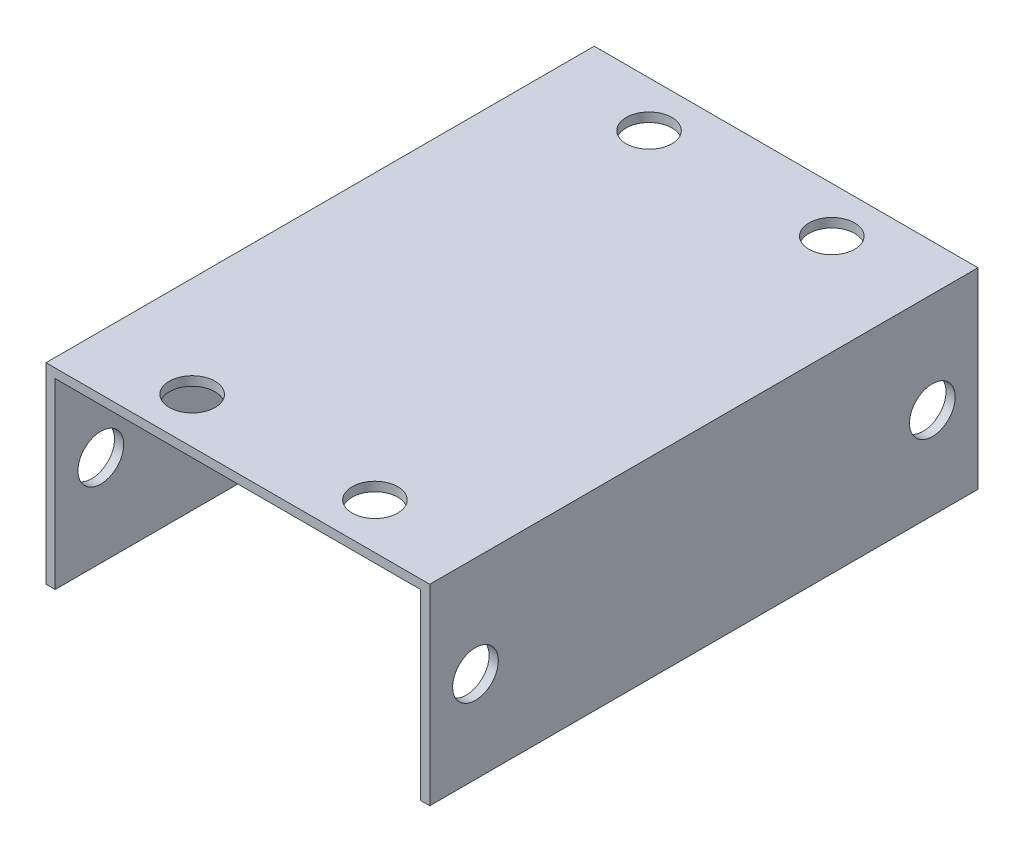
SolidWorks part; units mm, degrees
ref_plane "Front Plane" through (0, 0, 0) normal (0, 0, 1) x (1, 0, 0)
ref_plane "Top Plane" through (0, 0, 0) normal (0, 1, 0) x (1, 0, 0)
ref_plane "Right Plane" through (0, 0, 0) normal (1, 0, 0) x (0, 0, -1)
sketch "Sketch1" plane through (0, 0, 0) normal (0, 0, 1) x (1, 0, 0)
  line L0 (-20, -10) -> (20, -10) construction
  line L1 (-20, -10) -> (20, -10) construction
  line L2 (-20, -10) -> (-20, 10)
  line L3 (-20, 10) -> (20, 10)
  line L4 (20, -10) -> (20, 10)
  line L5 (-20, -10) -> (20, 10) construction
  line L6 (-20, 10) -> (20, -10) construction
  line L7 (-21, -10) -> (-20, -10)
  line L8 (-21, -10) -> (-21, 11)
  line L9 (-21, 11) -> (21, 11)
  line L10 (21, -10) -> (21, 11)
  line L11 (-21, -10) -> (21, 11) construction
  line L12 (-21, 11) -> (21, -10) construction
  line L13 (20, -10) -> (21, -10)
  point P0 (0, 0)
  point P6 (0, 0.5)
  point P11 (-3.491, 1.1742)
  point P12 (0, 0)
  point P13 (0, 0)
  point P14 (0, 0)
  dimension "D1" = 1
  dimension "D2" = 1
  dimension "D3" = 40
  dimension "D4" = 20
extrude "Boss-Extrude1" add sketch "Sketch1" along normal blind 60
sketch "Sketch2" plane through (0, 10, 0) normal (0, -1, 0) x (1, 0, 0)
  line L1 (-20, 60) -> (-20, 0) construction
  line L3 (-20, 0) -> (20, 0) construction
  line L4 (0, 30) -> (0, 0) construction
  line L5 (20, 60) -> (20, 0) construction
  line L6 (-20, 30) -> (20, 30) construction
  line L7 (-20, 5) -> (0, 5) construction
  circle A3 centre (-10, 5) radius 2.5
  circle A4 centre (10, 5) radius 2.5
  circle A5 centre (10, 55) radius 2.5
  circle A6 centre (-10, 55) radius 2.5
  point P20 (-11.2884, 5)
  dimension "D2" = 5
  dimension "D3" = 5
extrude "Cut-Extrude1" cut sketch "Sketch2" against normal through all
sketch "Sketch3" plane through (20, 0, 0) normal (-1, 0, 0) x (0, 0, 1)
  line L0 (5, 10) -> (5, -10) construction
  line L1 (60, 10) -> (0, 10) construction
  line L2 (60, -10) -> (0, -10) construction
  line L3 (30, 10) -> (30, -10) construction
  line L4 (0, 10) -> (0, -10) construction
  circle A0 centre (5, 0) radius 2.5
  circle A1 centre (55, 0) radius 2.5
  point P10 (0, 0)
  dimension "D1" = 5
  dimension "D2" = 5
extrude "Cut-Extrude2" cut sketch "Sketch3" against normal through all both and the other way through all
